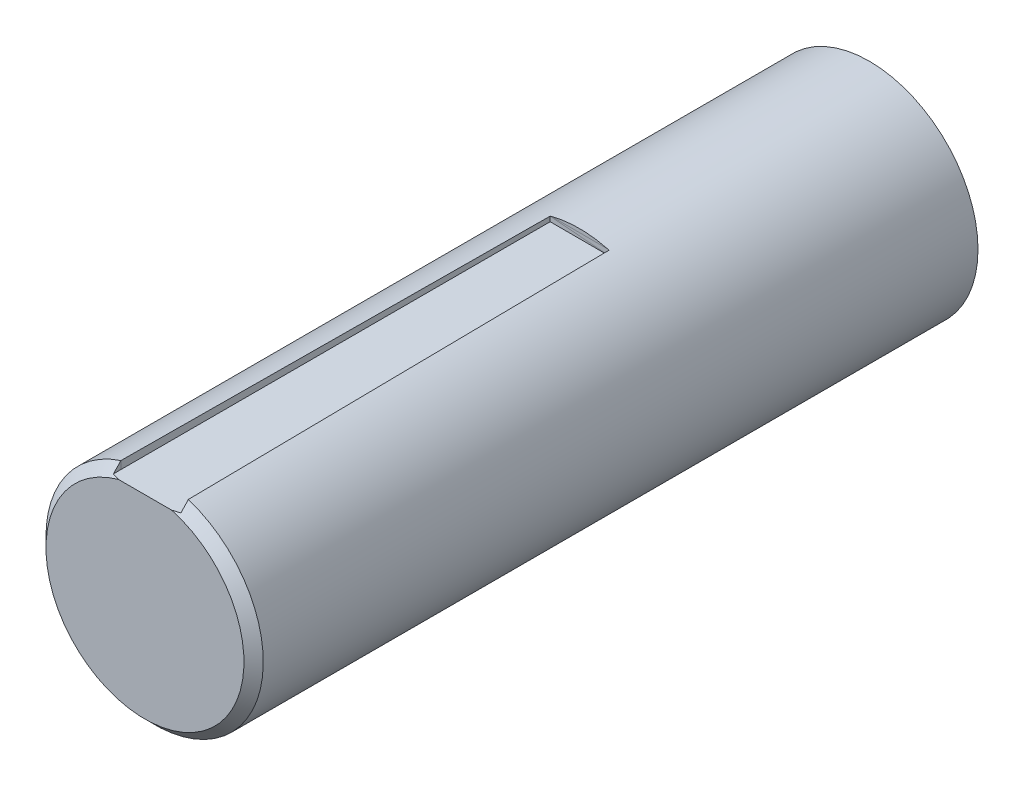
SolidWorks part; units mm, degrees
ref_plane "Front Plane" through (0, 0, 0) normal (0, 0, 1) x (1, 0, 0)
ref_plane "Top Plane" through (0, 0, 0) normal (0, 1, 0) x (1, 0, 0)
ref_plane "Right Plane" through (0, 0, 0) normal (1, 0, 0) x (0, 0, -1)
sketch "Sketch1" plane through (0, 0, 0) normal (0, 0, 1) x (1, 0, 0)
  circle A0 centre (0, 0) radius 22.5
extrude "Boss-Extrude1" add sketch "Sketch1" along normal blind 150
chamfer "Chamfer1" distance 2 angle 45 1 edges at (22.5, 0, 150)
sketch "Sketch3" plane through (0, 0, 150) normal (0, 0, 1) x (1, 0, 0)
  line L0 (0, 0) -> (0, 22.5)
  line L1 (0, 22.5) -> (7, 22.5)
  line L2 (0, 22.5) -> (-7, 22.5)
  line L3 (-7, 22.5) -> (-7, 19.75)
  line L4 (-7, 19.75) -> (7, 19.75)
  line L5 (7, 19.75) -> (7, 22.5)
  line L6 (-7, 22.5) -> (-7, 22.638)
  line L7 (-7, 22.638) -> (7, 22.638)
  line L8 (7, 22.638) -> (7, 22.5)
  circle A0 centre (0, 0) radius 22.5 construction
  circle M6 centre (0, 0) radius 20.5
  dimension "D1" = 7
  dimension "D2" = 7
  dimension "D3" = 2.75
extrude "Cut-Extrude6" cut sketch "Sketch3" against normal blind 90 draft 0.57 contours L3 L4 L0 L2 M6 | L4 L5 L1 L0 M6 | L8 L7 L6 L2 L1 | L4 L0 M6 | L0 L4 M6 region at (-2.0655, 20.0505, 150) region at (2.0655, 20.0505, 150) region at (-3.7398, 21.3046, 150) region at (3.7398, 21.3046, 150) region at (0, 22.569, 150)
sketch "Sketch6" plane through (0, 21.2402, 0.2113) normal (0, 1, 0.0099) x (1, 0, 0)
  line L0 (-6.9801, -147.7799) -> (6.9801, -147.7799)
  line L1 (6.9801, -147.7799) -> (6.1046, -59.7916)
  line L2 (6.1046, -59.7916) -> (-6.1046, -59.7816)
  line L3 (-6.1046, -59.7816) -> (-6.9801, -147.7799)
extrude "Cut-Extrude7" cut sketch "Sketch6" along normal blind 21 contours L3 L0 L1 L2
